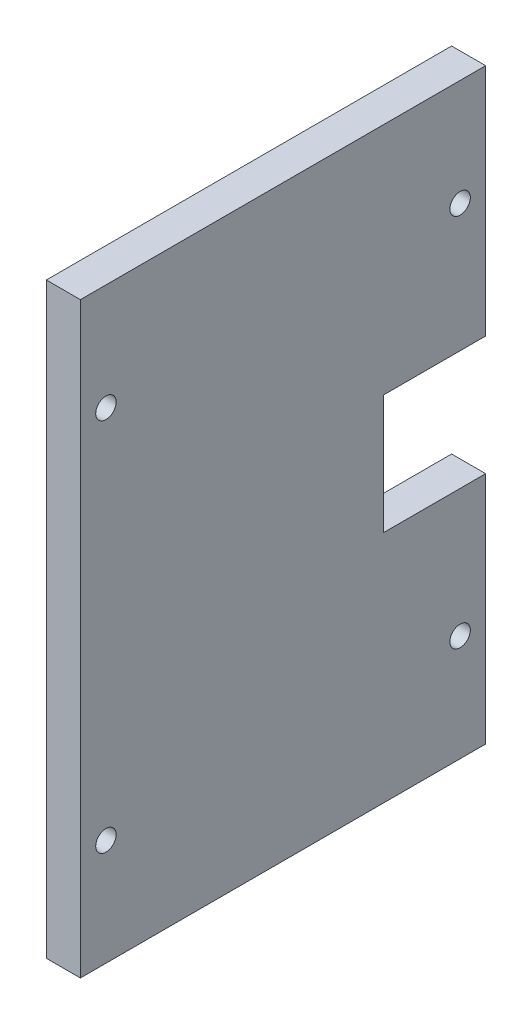
SolidWorks part; units mm, degrees
ref_plane "Front Plane" through (0, 0, 0) normal (0, 0, 1) x (1, 0, 0)
ref_plane "Top Plane" through (0, 0, 0) normal (0, 1, 0) x (1, 0, 0)
ref_plane "Right Plane" through (0, 0, 0) normal (1, 0, 0) x (0, 0, -1)
ref_plane "PZ_p126_200" through (0, 0, 126.2) normal (0, 0, 1) x (1, 0, 0)
sketch "S_box1" plane through (0, 0, 126.2) normal (0, 0, 1) x (1, 0, 0)
  line L0 (10.2, -34.5) -> (14.2, -34.5)
  line L1 (14.2, -34.5) -> (14.2, 34.5)
  line L2 (14.2, 34.5) -> (10.2, 34.5)
  line L3 (10.2, 34.5) -> (10.2, -34.5)
  dimension "P1" = 10.2
  dimension "P2" = 34.5
  dimension "P3" = 14.2
  dimension "P4" = 34.5
  dimension "P5" = 14.2
  dimension "P6" = 34.5
  dimension "P7" = 10.2
  dimension "P8" = 34.5
extrude "Boss_1" add sketch "S_box1" along normal blind 47.6
ref_plane "PZ_p126_100" through (0, 0, 126.1) normal (0, 0, 1) x (1, 0, 0)
sketch "S_cut2" plane through (0, 0, 126.1) normal (0, 0, 1) x (1, 0, 0)
  line L0 (10.1, -7) -> (14.3, -7)
  line L1 (14.3, -7) -> (14.3, 7)
  line L2 (14.3, 7) -> (10.1, 7)
  line L3 (10.1, 7) -> (10.1, -7)
  dimension "P1" = 10.1
  dimension "P2" = 7
  dimension "P3" = 14.3
  dimension "P4" = 7
  dimension "P5" = 14.3
  dimension "P6" = 7
  dimension "P7" = 10.1
  dimension "P8" = 7
extrude "Pocket_2" cut sketch "S_cut2" along normal blind 12.1
ref_plane "PX_p10_100" through (10.1, 0, 0) normal (1, 0, 0) x (0, 0, -1)
sketch "S_hole3" plane through (10.1, 0, 0) normal (1, 0, 0) x (0, 0, -1)
  circle A0 centre (-129.2, -22) radius 1.2
  dimension "D1_S_hole3" = 2.4
  dimension "P2" = 129.2
  dimension "P3" = 22
extrude "Hole_3" cut sketch "S_hole3" along normal blind 4.2
sketch "S_hole4" plane through (10.1, 0, 0) normal (1, 0, 0) x (0, 0, -1)
  circle A0 centre (-129.2, -22) radius 2.3
  dimension "D1_S_hole4" = 4.6
  dimension "P2" = 129.2
  dimension "P3" = 22
extrude "Hole_4" cut sketch "S_hole4" along normal blind 1.4
sketch "S_hole5" plane through (10.1, 0, 0) normal (1, 0, 0) x (0, 0, -1)
  circle A0 centre (-170.8, -22) radius 1.2
  dimension "D1_S_hole5" = 2.4
  dimension "P2" = 170.8
  dimension "P3" = 22
extrude "Hole_5" cut sketch "S_hole5" along normal blind 4.2
sketch "S_hole6" plane through (10.1, 0, 0) normal (1, 0, 0) x (0, 0, -1)
  circle A0 centre (-170.8, -22) radius 2.3
  dimension "D1_S_hole6" = 4.6
  dimension "P2" = 170.8
  dimension "P3" = 22
extrude "Hole_6" cut sketch "S_hole6" along normal blind 1.4
sketch "S_hole7" plane through (10.1, 0, 0) normal (1, 0, 0) x (0, 0, -1)
  circle A0 centre (-129.2, 22) radius 1.2
  dimension "D1_S_hole7" = 2.4
  dimension "P2" = 129.2
  dimension "P3" = 22
extrude "Hole_7" cut sketch "S_hole7" along normal blind 4.2
sketch "S_hole8" plane through (10.1, 0, 0) normal (1, 0, 0) x (0, 0, -1)
  circle A0 centre (-129.2, 22) radius 2.3
  dimension "D1_S_hole8" = 4.6
  dimension "P2" = 129.2
  dimension "P3" = 22
extrude "Hole_8" cut sketch "S_hole8" along normal blind 1.4
sketch "S_hole9" plane through (10.1, 0, 0) normal (1, 0, 0) x (0, 0, -1)
  circle A0 centre (-170.8, 22) radius 1.2
  dimension "D1_S_hole9" = 2.4
  dimension "P2" = 170.8
  dimension "P3" = 22
extrude "Hole_9" cut sketch "S_hole9" along normal blind 4.2
sketch "S_hole10" plane through (10.1, 0, 0) normal (1, 0, 0) x (0, 0, -1)
  circle A0 centre (-170.8, 22) radius 2.3
  dimension "D1_S_hole10" = 4.6
  dimension "P2" = 170.8
  dimension "P3" = 22
extrude "Hole_10" cut sketch "S_hole10" along normal blind 1.4
equation "\"plate_t\" = 3"
equation "\"clearance\" = 0.5"
